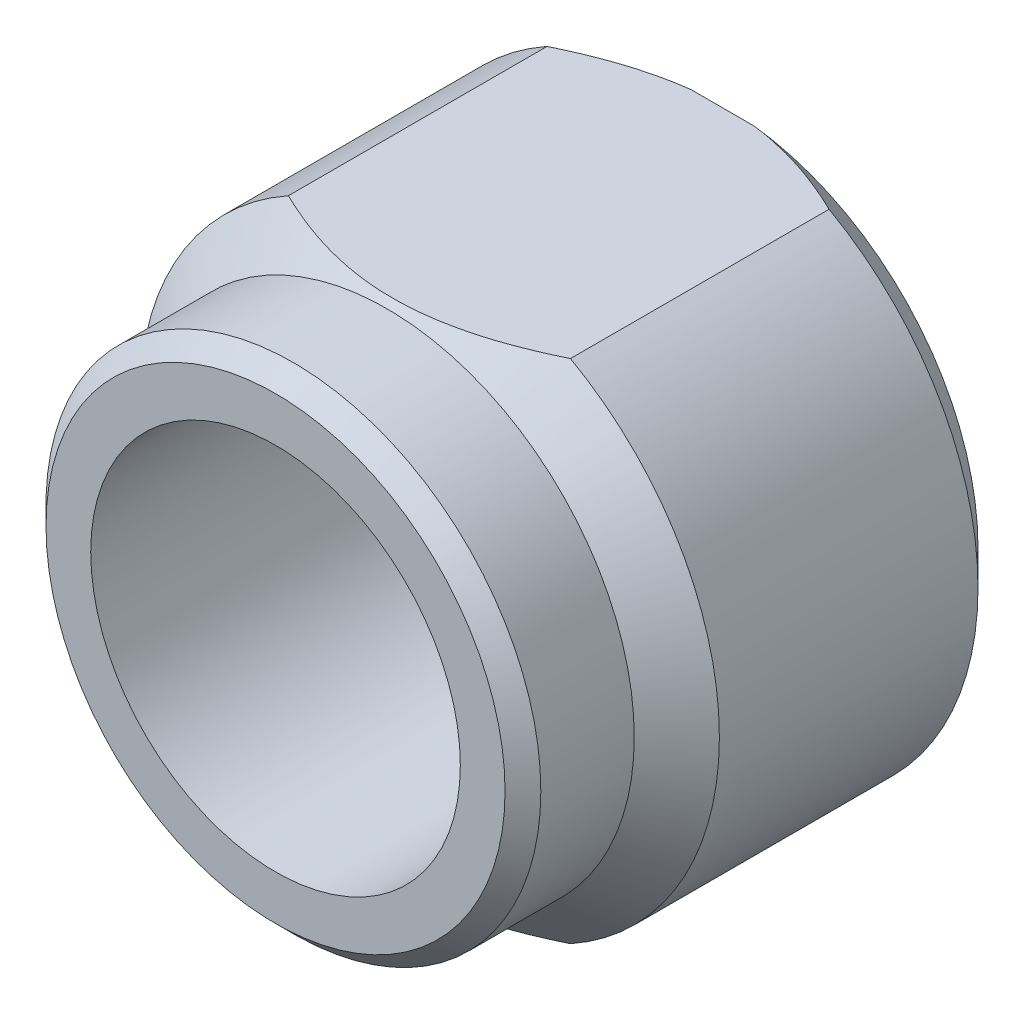
SolidWorks part; units mm, degrees
ref_plane "Front Plane" through (0, 0, 0) normal (0, 0, 1) x (1, 0, 0)
ref_plane "Top Plane" through (0, 0, 0) normal (0, 1, 0) x (1, 0, 0)
ref_plane "Right Plane" through (0, 0, 0) normal (1, 0, 0) x (0, 0, -1)
sketch "Sketch1" plane through (0, 0, 0) normal (1, 0, 0) x (0, 0, -1)
  line L0 (-2.3, 0) -> (-2.3, 3.1)
  line L1 (-2.3, 3.1) -> (-7.5, 3.1)
  line L2 (-7.5, 3.1) -> (-7.5, 3.85)
  line L3 (-7.5, 3.85) -> (-7.2, 4.15)
  line L4 (-7.2, 4.15) -> (-5.633, 4.15)
  line L5 (-5.633, 4.15) -> (-4.919, 4.864)
  line L6 (-4.919, 4.864) -> (-0.581, 4.864)
  line L7 (-0.581, 4.864) -> (0, 4.283)
  line L8 (0, 4.283) -> (0, 0)
  line L9 (0, 0) -> (-2.3, 0)
  line L10 (0, 0) -> (-2.3, 0) construction
revolve "Revolve1" add sketch "Sketch1" angle 360 about L10 reverse direction yes
cosmetic thread "Cosmetic Thread1"
sketch "Sketch2" plane through (0, 0, 0) normal (1, 0, 0) x (0, 0, -1)
  line L0 (-1.5, -0.3688) -> (0, -0.5)
  line L1 (0, -0.5) -> (0, 0.5)
  line L2 (0, 0.5) -> (-1.5, 0.3688)
  line L3 (-1.5, 0.3688) -> (-1.5, -0.3688)
extrude "Cut-Extrude1" cut sketch "Sketch2" along normal blind 3.1 and the other way blind 3.1
sketch "Sketch3" plane through (0, 0, 0) normal (0, 0, 1) x (1, 0, 0)
  line L0 (-12, 6) -> (-12, -6)
  line L1 (-12, -6) -> (12, -6)
  line L2 (12, -6) -> (12, 6)
  line L3 (12, 6) -> (-12, 6)
  line L4 (-10, 4.25) -> (-10, -4.25)
  line L5 (-10, -4.25) -> (10, -4.25)
  line L6 (10, -4.25) -> (10, 4.25)
  line L7 (10, 4.25) -> (-10, 4.25)
extrude "Cut-Extrude2" cut sketch "Sketch3" along normal blind 7.5
ref_plane "FILTERNIPPEL XY" through (0, 0, 0) normal (0, 0, 1) x (1, 0, 0)
ref_plane "FILTERNIPPEL XZ" through (0, 0, 0) normal (0, -1, 0) x (-1, 0, 0)
ref_plane "FILTERNIPPEL YZ" through (0, 0, 0) normal (1, 0, 0) x (0, 0, -1)
ref_axis "FILTERNIPPEL X" through (-80.9, 0, 0) along (1, 0, 0)
ref_axis "FILTERNIPPEL Y" through (0, -50, 0) along (0, 1, 0)
ref_axis "FILTERNIPPEL Z" through (0, 0, 80.9) along (0, 0, -1)
sketch3d "FILTERNIPPEL"
  point P0 (0, 0, 0)
other "Freeze***"
